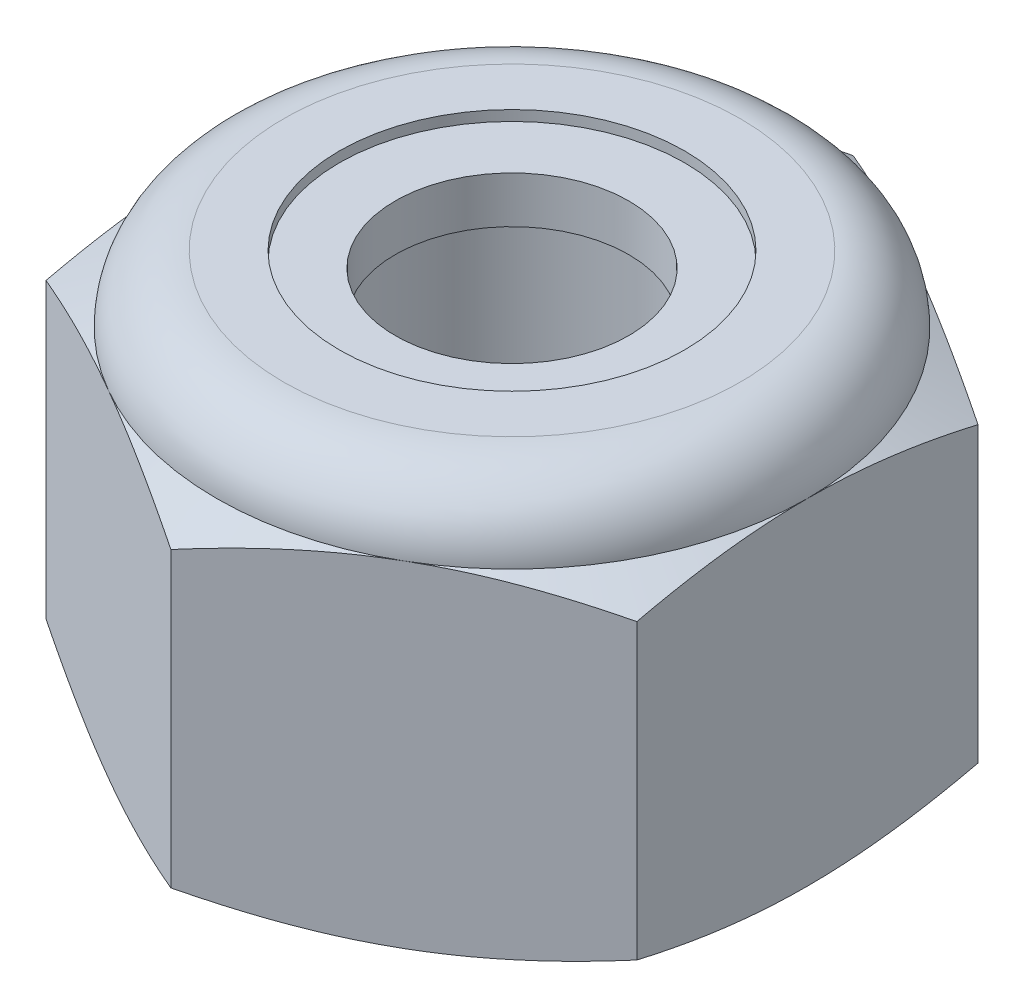
SolidWorks part; units mm, degrees
ref_plane "Front" through (0, 0, 0) normal (0, 0, 1) x (1, 0, 0)
ref_plane "Top" through (0, 0, 0) normal (0, 1, 0) x (1, 0, 0)
ref_plane "Right" through (0, 0, 0) normal (1, 0, 0) x (0, 0, -1)
sketch "Sketch1" plane through (0, 0, 0) normal (0, 1, 0) x (1, 0, 0)
  line L1 (0, 5.041) -> (-4.3656, 2.5205)
  line L2 (-4.3656, 2.5205) -> (-4.3656, -2.5205)
  line L3 (-4.3656, -2.5205) -> (0, -5.041)
  line L4 (0, -5.041) -> (4.3656, -2.5205)
  line L5 (4.3656, -2.5205) -> (4.3656, 2.5205)
  line L6 (4.3656, 2.5205) -> (0, 5.041)
  circle A0 centre (0, 0) radius 4.3656 construction
  dimension "Hex Flats" = 8.7312
extrude "Extrude1" add sketch "Sketch1" along normal blind 5.9531
sketch "Sketch2" plane through (0, 0, 0) normal (1, 0, 0) x (0, 0, -1)
  line L0 (-2.0828, 0) -> (-2.0828, 5.9531) construction
  line L1 (0, 0) -> (2.0828, 0)
  line L2 (0, 0) -> (0, 5.9531)
  line L3 (0, 5.9531) -> (2.0828, 5.9531)
  line L4 (2.0828, 0) -> (2.0828, 5.9531)
  line L5 (-2.5205, 5.9531) -> (2.5205, 5.9531) construction
  line L7 (0, -2.0828) -> (0, 0) construction
  dimension "Thread Dia" = 4.1656
revolve "Revolve1" add sketch "Sketch2" angle 360 about L7
sketch "Sketch3" plane through (0, 0, 0) normal (1, 0, 0) x (0, 0, -1)
  line L0 (2.0828, 5.9531) -> (-2.0828, 5.9531) construction
  line L1 (-2.0828, 5.9531) -> (-2.0828, 5.1594) construction
  line L2 (-2.0828, 5.1594) -> (2.0828, 5.9531) construction
  line L3 (2.0828, 5.9531) -> (2.1014, 5.8557) construction
  line L4 (2.1014, 5.8557) -> (2.2314, 5.1734)
  line L5 (2.2314, 5.1734) -> (1.7629, 5.3366)
  line L6 (1.7629, 5.3366) -> (1.7258, 5.5316)
  line L7 (1.7258, 5.5316) -> (2.1014, 5.8557)
  line L8 (1.7443, 5.4341) -> (2.1664, 5.5145) construction
  line L9 (2.0828, 5.9531) -> (2.0828, 5.4986) construction
  line L10 (2.0828, 5.4986) -> (-2.0828, 4.7049) construction
  line L11 (-2.0828, 4.7049) -> (-2.0828, 5.1594) construction
  line L12 (-0.1622, 5.9531) -> (0.1622, 4.2503) construction
  line L13 (-2.0828, 0) -> (-2.0828, 5.9531) construction
  line L14 (0, 5.9531) -> (2.0828, 5.9531) construction
  line L15 (2.0828, 0) -> (2.0828, 5.9531) construction
  point P13 (0, 5.1017)
  dimension "D1" = 0.0992
  dimension "D2" = 0.1984
  dimension "Thread Pitch" = 0.7937
  dimension "D4" = 60
  dimension "D5" = 0.7937
revolve "Cut-Revolve1" [suppressed] cut sketch "Sketch3" angle 360 about L12
pattern_linear "LPattern1" [suppressed] count 8 spacing 0.7937 along (0, -1, 0) count 2 spacing 0.7937 along (0, 1, 0) of bodies 110
sketch "Sketch4" plane through (0, 0, 0) normal (1, 0, 0) x (0, 0, -1)
  line L0 (0, 5.9531) -> (2.0828, 5.9531)
  line L1 (2.0828, 5.9531) -> (1.7258, 5.7866)
  line L2 (1.7258, 5.7866) -> (1.7258, 0.1665)
  line L3 (1.7258, 0.1665) -> (2.0828, 0)
  line L4 (2.0828, 0) -> (0, 0)
  line L5 (0, 0) -> (0, 5.9531)
  line L6 (2.0828, 0) -> (2.0828, 5.9531) construction
  line L7 (0, 5.9531) -> (2.0828, 5.9531) construction
  line L8 (0, 0) -> (2.0828, 0) construction
  line L9 (0, 0) -> (0, 5.9531) construction
  line L10 (0, 5.9531) -> (0, 6.3471) construction
  dimension "D1" = 25
revolve "Cut-Revolve2" cut sketch "Sketch4" angle 360 about L10
combine bodies "Combine1" operation type subtract main body 112 bodies to subtract 109
sketch "Sketch5" plane through (0, 0, 0) normal (1, 0, 0) x (0, 0, -1)
  line L0 (0, 0) -> (4.3656, 0)
  line L1 (4.3656, 0) -> (5.041, 0.3149)
  line L2 (5.041, 0.3149) -> (5.041, 4.646)
  line L3 (5.041, 4.646) -> (4.3656, 4.9609)
  line L4 (3.3734, 5.9531) -> (3.3734, 7.2231)
  line L5 (3.3734, 7.2231) -> (6.311, 7.2231)
  line L6 (6.311, 7.2231) -> (6.311, -1.27)
  line L7 (6.311, -1.27) -> (0, -1.27)
  line L8 (0, -1.27) -> (0, 0)
  line L9 (4.3656, 4.9609) -> (4.3656, 0) construction
  line L10 (0, 0) -> (2.0828, 0) construction
  line L13 (5.041, 2.4805) -> (6.311, 2.4805) construction
  line L14 (5.041, 5.9531) -> (5.041, 0) construction
  line L15 (0, 0) -> (0, 7.2231) construction
  line L20 (0, 7.2231) -> (3.3734, 7.2231) construction
  line L22 (0, 5.9531) -> (2.0828, 5.9531) construction
  arc A0 (4.3656, 4.9609) -> (3.3734, 5.9531) centre (3.3734, 4.9609) ccw
  dimension "D1" = 25
  dimension "D2" = 1.27
  dimension "D3" = 5.9531
  dimension "D4" = 0.9922
revolve "Cut-Revolve3" cut sketch "Sketch5" angle 360 about L15
sketch "Sketch6" plane through (0, 0, 0) normal (1, 0, 0) x (0, 0, -1)
  line L0 (0, 4.9609) -> (4.2132, 4.9609)
  line L1 (3.3734, 5.8007) -> (2.5496, 5.8007)
  line L2 (0, 7.2231) -> (0, 4.9609)
  line L3 (2.5496, 7.2231) -> (0, 7.2231)
  line L4 (0, 7.2231) -> (3.3734, 7.2231) construction
  line L5 (0, 0) -> (0, 7.2231) construction
  line L6 (0, 7.2231) -> (0, 44.323) construction
  line L7 (2.5496, 5.8007) -> (2.5496, 7.2231)
  line L8 (3.3734, 5.9531) -> (3.3734, 5.8007) construction
  line L9 (2.5496, 5.8007) -> (1.7258, 5.8007) construction
  line L10 (1.7258, 5.8007) -> (1.7258, 5.7866) construction
  arc A0 (4.2132, 4.9609) -> (3.3734, 5.8007) centre (3.3734, 4.9609) ccw
  arc A1 (4.3656, 4.9609) -> (3.3734, 5.9531) centre (3.3734, 4.9609) ccw construction
  dimension "D1" = 0.1524
revolve "Cut-Revolve4" cut sketch "Sketch6" angle 360 about L6
sketch "Sketch7" plane through (0, 0, 0) normal (1, 0, 0) x (0, 0, -1)
  line L0 (1.7258, 5.0371) -> (4.1332, 5.0371)
  line L1 (3.3734, 5.7245) -> (1.7258, 5.7245)
  line L2 (1.7258, 5.7245) -> (1.7258, 5.0371)
  line L3 (1.7258, 5.0371) -> (0, 5.0371) construction
  line L4 (0, 5.0371) -> (0, 5.7245) construction
  line L5 (0, 5.7245) -> (1.7258, 5.7245) construction
  line L6 (1.7258, 5.0371) -> (1.7258, 4.9609) construction
  line L7 (0, 4.9609) -> (4.2132, 4.9609) construction
  line L8 (3.3734, 5.7245) -> (3.3734, 5.8007) construction
  arc A0 (4.1332, 5.0371) -> (3.3734, 5.7245) centre (3.3734, 4.9609) ccw
  arc A2 (4.2132, 4.9609) -> (3.3734, 5.8007) centre (3.3734, 4.9609) ccw construction
  dimension "D1" = 0.0762
revolve "Revolve2" add sketch "Sketch7" angle 360 about L4
equation "\"D1@Sketch3\"=\"Thread Pitch@Sketch3\"/8"
equation "\"D2@Sketch3\"=\"Thread Pitch@Sketch3\"/4"
equation "\"D5@Sketch3\"=\"Thread Pitch@Sketch3\""
equation "\"D4@LPattern1\"=\"Thread Pitch@Sketch3\""
equation "\"D3@LPattern1\"=\"Thread Pitch@Sketch3\""
equation "\"D1@LPattern1\"=\"Height@Extrude1\"/\"Thread Pitch@Sketch3\""
equation "\"D4@Sketch5\"=\"Height@Extrude1\"/6"
